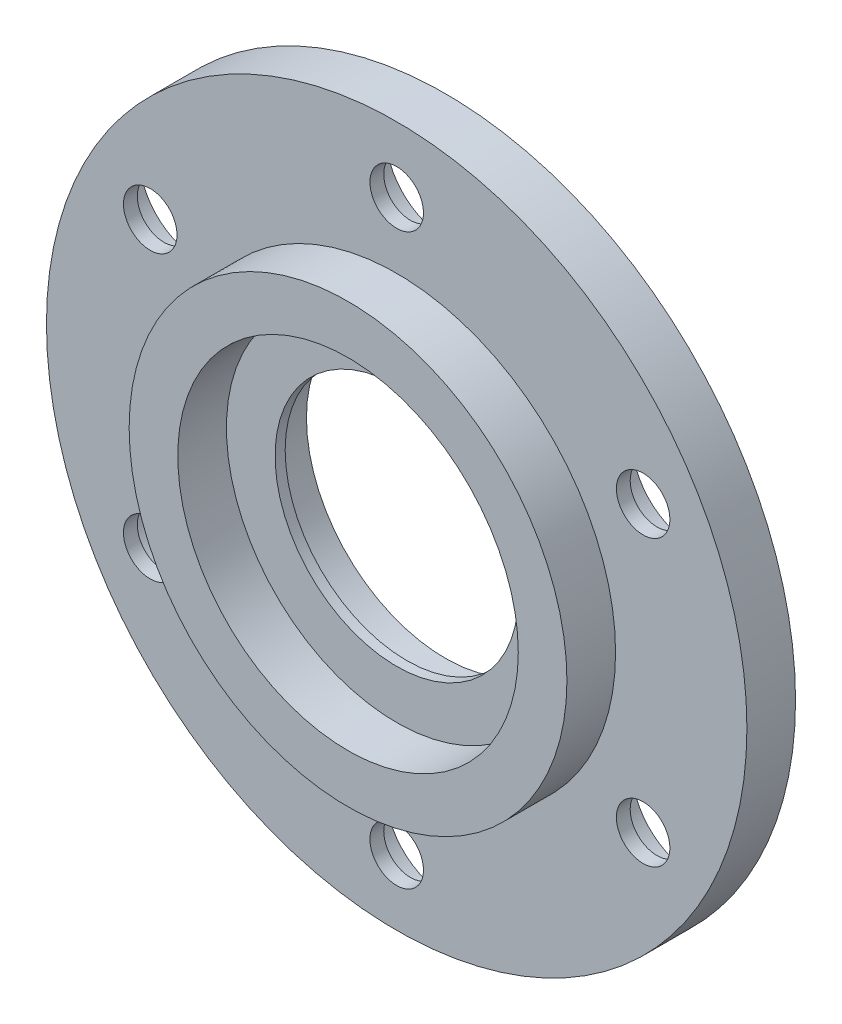
SolidWorks part; units mm, degrees
material "6061-T6 (SS)"
ref_plane "Front Plane" through (0, 0, 0) normal (0, 0, 1) x (1, 0, 0)
ref_plane "Top Plane" through (0, 0, 0) normal (0, 1, 0) x (1, 0, 0)
ref_plane "Right Plane" through (0, 0, 0) normal (1, 0, 0) x (0, 0, -1)
sketch "Sketch Spindle Skeleton" plane through (0, 0, 0) normal (1, 0, 0) x (0, 0, -1)
  line L0 (-109.9, -9.5) -> (-134, -9.5)
  line L5 (-1000, 0) -> (49000, 0)
  line L6 (0, -9.5) -> (0, 9.5)
  line L13 (0, 9.5) -> (-48.3, 9.5)
  line L26 (-48.3, 9.5) -> (-48.3, 14)
  line L27 (-48.3, 14) -> (-109.9, 14)
  line L32 (-109.9, 14) -> (-109.9, 9.5)
  line L34 (-150, 7) -> (-150, -7)
  line L36 (-109.9, -9.5) -> (-109.9, -14)
  line L37 (-109.9, -14) -> (-48.3, -14)
  line L38 (-48.3, -14) -> (-48.3, -9.5)
  line L39 (0, -9.5) -> (-48.3, -9.5)
  line L40 (-24.2, 36) -> (-19.2, 36)
  line L41 (-126.5, 22.5) -> (-109.9, 22.5)
  line L42 (-126.5, 22.5) -> (-126.5, -22.5)
  line L43 (-126.5, -22.5) -> (-109.9, -22.5)
  line L44 (-109.9, 22.5) -> (-109.9, -22.5)
  line L45 (-126.5, 22.5) -> (-109.9, -22.5) construction
  line L46 (-126.5, -22.5) -> (-109.9, 22.5) construction
  line L47 (-31.7, 22.5) -> (-48.3, 22.5)
  line L48 (-31.7, 22.5) -> (-31.7, -22.5)
  line L49 (-31.7, -22.5) -> (-48.3, -22.5)
  line L50 (-48.3, 22.5) -> (-48.3, -22.5)
  line L51 (-31.7, 22.5) -> (-48.3, -22.5) construction
  line L52 (-31.7, -22.5) -> (-48.3, 22.5) construction
  line L59 (-19.2, 36) -> (-19.2, -36)
  line L60 (-19.2, -36) -> (-24.2, -36)
  line L61 (-24.2, -22.5) -> (-29.2, -22.5)
  line L62 (-29.2, -22.5) -> (-29.2, -17.5)
  line L63 (-29.2, -17.5) -> (-24.2, -17.5)
  line L64 (-24.2, -17.5) -> (-24.2, 17.5)
  line L65 (-24.2, 17.5) -> (-29.2, 17.5)
  line L66 (-29.2, 17.5) -> (-29.2, 22.5)
  line L67 (-29.2, 22.5) -> (-24.2, 22.5)
  line L68 (-24.2, 22.5) -> (-24.2, 36)
  line L69 (-24.2, -22.5) -> (-24.2, -36)
  line L71 (-131.5, 36) -> (-25.2, 36)
  line L72 (-131.5, 36) -> (-131.5, -36)
  line L73 (-131.5, -36) -> (-25.2, -36)
  line L74 (-25.2, 36) -> (-25.2, -36)
  line L75 (-131.5, 36) -> (-25.2, -36) construction
  line L76 (-131.5, -36) -> (-25.2, 36) construction
  line L77 (-134, -9.5) -> (-134, -7)
  line L78 (-134, -7) -> (-150, -7)
  line L79 (-109.9, 9.5) -> (-134, 9.5)
  line L80 (-134, 7) -> (-150, 7)
  line L81 (-134, 9.5) -> (-134, 7)
  line L82 (-121.95, 9.5) -> (-121.95, -9.5) construction
  line L83 (-24.15, 9.5) -> (-24.15, -9.5) construction
  point P3 (0, 0)
  point P18 (-118.2, 0)
  point P24 (-40, 0)
  point P29 (-78.35, 0)
  point P48 (-19.2, 29.25)
revolve "Main Revolve" add sketch "Sketch Spindle Skeleton" angle 360 about L5 region at (0, 22.65, 21.8091) region at (0, 20, 27.2)
sketch "Sketch Center Cut" plane through (0, 0, 24.2) normal (0, 0, 1) x (1, 0, 0)
  circle A0 centre (0, 0) radius 17.5 construction
  circle A1 centre (0, 0) radius 17.5 construction
  circle A2 centre (0, 0) radius 12.5
  dimension "D1" = 5
extrude "Cut Center" cut sketch "Sketch Center Cut" against normal through all
hole_wizard "CBORE for M5 Hex Head Bolt1" positions "Hole wizard sketch 1" profile "Hole wizard sketch 2" counterbore size "M5" standard "ANSI Metric" end condition through all
sketch "Hole wizard sketch 1" plane through (0, 0, 19.2) normal (0, 0, -1) x (-1, 0, 0)
  point P0 (0, 29.25)
sketch "Hole wizard sketch 2" plane through (0, 29.25, 19.2) normal (1, 0, 0) x (0, 1, 0)
  line L0 (0, 0) -> (0, 10)
  line L1 (0, 10) -> (2.75, 10)
  line L3 (2.75, 10) -> (2.75, 3.58)
  line L4 (2.75, 3.58) -> (6.12, 3.58)
  line L5 (6.12, 3.58) -> (6.12, 0)
  line L7 (6.12, 0) -> (0, 0)
  line L11 (0, -6.35) -> (0, 107.95) construction
  dimension "Thru Hole Dia." = 5.5
  dimension "Thru Hole Depth" = 10
  dimension "C'Bore Dia." = 12.24
  dimension "C'Bore Depth" = 3.58
pattern_circular "CirPattern1" count 6 over 360 about axis through (0, 0, 19.2) along (0, 0, 1) of "CBORE for M5 Hex Head Bolt1"
sketch "Sketch1" plane through (0, 0, 19.2) normal (0, 0, -1) x (-1, 0, 0)
  circle A0 centre (0, 0) radius 14.2748
  point P3 (0, 0)
  dimension "D1" = 28.5496
extrude "Cut-Extrude1" cut sketch "Sketch1" against normal blind 3.9624
